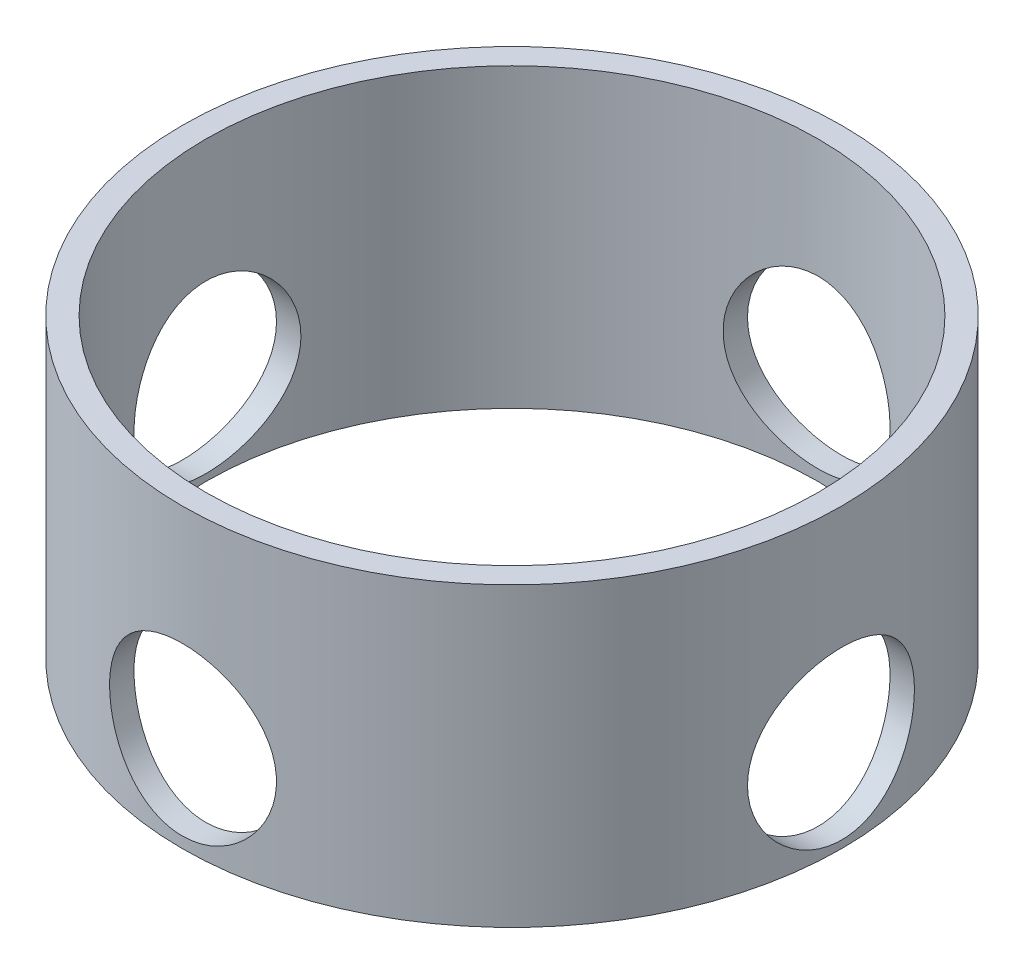
SolidWorks part; units mm, degrees
ref_plane "Front Plane" through (0, 0, 0) normal (0, 0, 1) x (1, 0, 0)
ref_plane "Top Plane" through (0, 0, 0) normal (0, 1, 0) x (1, 0, 0)
ref_plane "Right Plane" through (0, 0, 0) normal (1, 0, 0) x (0, 0, -1)
sketch "Sketch1" plane through (0, 0, 0) normal (0, 1, 0) x (1, 0, 0)
  circle A0 centre (0, 0) radius 88.9
  dimension "D1" = 177.8
extrude "Boss-Extrude1" add sketch "Sketch1" along normal blind 80
sketch "Sketch2" plane through (0, 0, 0) normal (0, 1, 0) x (1, 0, 0)
  circle A0 centre (0, 0) radius 82.55
  dimension "D1" = 165.1
extrude "Cut-Extrude4" cut sketch "Sketch2" along normal blind 90 contours A0
sketch "Sketch12" plane through (0, 0, 0) normal (1, 0, 0) x (0, 0, -1)
  circle A0 centre (0, 24.3361) radius 22.5
  dimension "D1" = 45
extrude "Cut-Extrude5" cut sketch "Sketch12" against normal blind 115.64
sketch "Sketch13" plane through (0, 0, 0) normal (0, 0, 1) x (1, 0, 0)
  circle A0 centre (0, 25.4507) radius 22.5
extrude "Cut-Extrude6" cut sketch "Sketch13" against normal blind 115.64
sketch "Sketch14" plane through (0, 0, 0) normal (1, 0, 0) x (0, 0, -1)
  circle A0 centre (0, 24.5219) radius 22.5
extrude "Cut-Extrude7" cut sketch "Sketch14" along normal blind 99.64
sketch "Sketch15" plane through (0, 0, 0) normal (0, 0, 1) x (1, 0, 0)
  circle A0 centre (0, 25.4507) radius 22.5
extrude "Cut-Extrude8" cut sketch "Sketch15" along normal blind 137.64
ref_axis "Axis1" through (0, 25.4507, 88.9) along (0, 0, 1)
